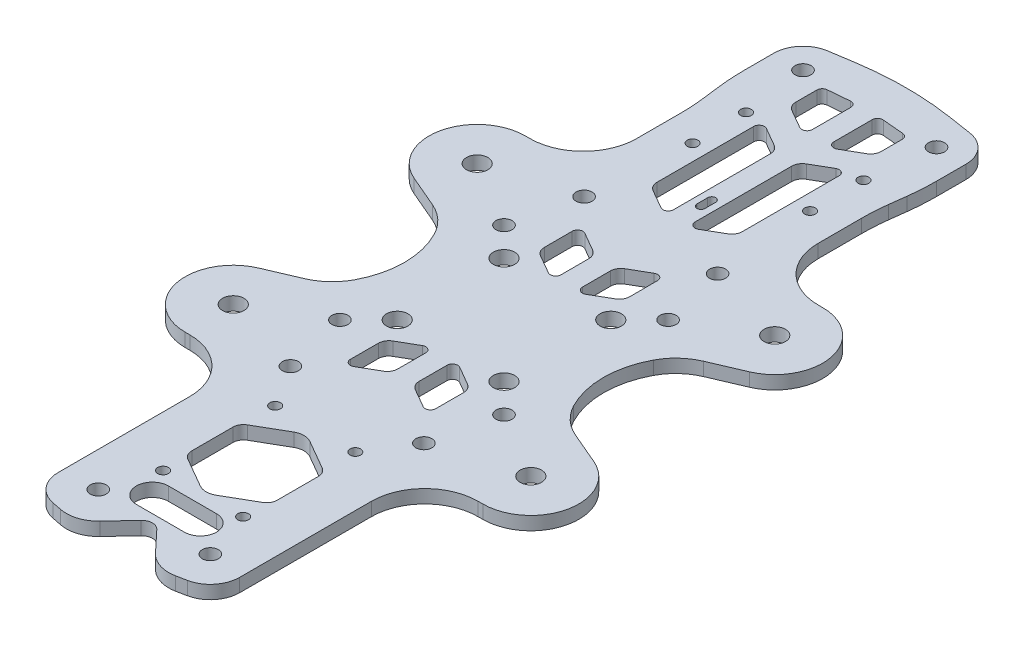
SolidWorks part; units mm, degrees
other "Markup1"
sketch "Sketch3" plane through (-36.8644, 3, -75.3176) normal (0, 1, 0) x (1, 0, 0)
material "Thornel Mat VMA"
ref_plane "Front Plane" through (0, 0, 0) normal (0, 0, 1) x (1, 0, 0)
ref_plane "Top Plane" through (0, 0, 0) normal (0, 1, 0) x (1, 0, 0)
ref_plane "Right Plane" through (0, 0, 0) normal (1, 0, 0) x (0, 0, -1)
sketch "Sketch1" plane through (0, 0, 0) normal (0, 1, 0) x (1, 0, 0)
  line L0 (7.0144, -13.8425) -> (3.5179, -11.8157)
  line L1 (-1.9927, -17.8721) -> (-1.9837, -12.6721)
  line L2 (-6.9856, 13.8181) -> (-3.4821, 11.8035)
  line L3 (2.0122, 17.9008) -> (2.0164, 12.6801)
  line L4 (2, 51.8812) -> (2, 33.7679)
  line L5 (-7, 34.9226) -> (-3.5, 32.9019)
  line L6 (3.5, 58.9019) -> (7, 60.9226)
  line L7 (-7, 60.9226) -> (-3.5, 58.9019)
  line L8 (-1.5, -37.866) -> (-7, -41.0415)
  line L9 (-6.6638, -69.1081) -> (-2.9181, -65.1127)
  line L10 (2.0164, -12.6801) -> (2.0122, -17.9008)
  line L11 (3, -19.6132) -> (6.5, -21.634)
  line L12 (8.002, -20.7686) -> (8.0113, -15.5764)
  line L13 (-3.4821, -11.8035) -> (-6.9856, -13.8181)
  line L14 (-7.9886, -15.5483) -> (-7.9977, -20.7675)
  line L15 (-6.5, -21.634) -> (-3, -19.6133)
  line L16 (-1.9837, 12.6721) -> (-1.9927, 17.8721)
  line L17 (-3, 19.6133) -> (-6.5, 21.634)
  line L18 (-7.9977, 20.7675) -> (-7.9886, 15.5483)
  line L19 (3.5179, 11.8157) -> (7.0144, 13.8425)
  line L20 (8.0113, 15.5764) -> (8.002, 20.7686)
  line L21 (6.5, 21.634) -> (3, 19.6132)
  line L22 (3.5, 32.9019) -> (7, 34.9226)
  line L23 (8, 36.6547) -> (8, 54.7679)
  line L24 (6.5, 55.634) -> (3, 53.6132)
  line L25 (-2, 33.7679) -> (-2, 51.8812)
  line L26 (-3, 53.6133) -> (-6.5, 55.634)
  line L27 (-8, 54.7679) -> (-8, 36.6546)
  line L28 (8, 62.6547) -> (8, 66.5946)
  line L29 (7.0872, 67.5908) -> (3.0872, 67.9408)
  line L30 (2, 66.9446) -> (2, 59.7679)
  line L31 (-2, 59.7679) -> (-2, 66.9446)
  line L32 (-3.0872, 67.9408) -> (-7.0872, 67.5908)
  line L33 (-8, 66.5946) -> (-8, 62.6547)
  line L34 (-8, -42.7735) -> (-8, -50.4641)
  line L35 (-7, -52.1962) -> (-1.5, -55.3716)
  line L36 (1.5, -55.3716) -> (7, -52.1962)
  line L37 (8, -50.4641) -> (8, -42.7735)
  line L38 (7, -41.0415) -> (1.5, -37.866)
  line L39 (-12.1839, -69.9325) -> (-10.3636, -70.2952)
  line L40 (-15, -41.84) -> (-15, -66.5)
  line L41 (-27.8644, -29.84) -> (-27, -29.84)
  line L42 (-24.6147, -13.8367) -> (-30.6171, -16.404)
  line L43 (-30.6171, 16.404) -> (-24.6147, 13.8367)
  line L44 (-26.9944, 29.84) -> (-27.8644, 29.84)
  line L45 (-14.9906, 49.9801) -> (-14.9944, 41.8344)
  line L46 (-15.6838, 58.0267) -> (-15.3029, 54.9969)
  line L47 (-16, 68.4976) -> (-15.9961, 62.9879)
  line L48 (-8.6637, 72.6434) -> (-13.0415, 71.9578)
  line L49 (13.0415, 71.9578) -> (8.6635, 72.6434)
  line L50 (15.9961, 62.9879) -> (15.9999, 68.4976)
  line L51 (15.3029, 54.9969) -> (15.6838, 58.0267)
  line L52 (14.9944, 41.8344) -> (14.9906, 49.98)
  line L53 (27.8644, 29.84) -> (26.9944, 29.84)
  line L54 (24.6147, 13.8367) -> (30.6171, 16.404)
  line L55 (30.6171, -16.404) -> (24.6147, -13.8367)
  line L56 (27, -29.84) -> (27.8644, -29.84)
  line L57 (15, -66.5) -> (15, -41.84)
  line L58 (10.3636, -70.2952) -> (12.1839, -69.9325)
  line L59 (2.9181, -65.1127) -> (6.6638, -69.1081)
  circle A0 centre (15.365, 15.365) radius 1.5
  circle A1 centre (15.365, -15.365) radius 1.5
  circle A2 centre (-15.365, -15.365) radius 1.5
  circle A3 centre (-15.365, 15.365) radius 1.5
  circle A4 centre (27.8644, -22.84) radius 2
  circle A5 centre (27.8644, 22.84) radius 2
  circle A6 centre (10.5, -65.5) radius 1.5
  circle A7 centre (-10, 10) radius 2
  circle A8 centre (-10, -10) radius 2
  circle A9 centre (-10.5, -65.5) radius 1.5
  circle A10 centre (-27.8644, -22.84) radius 2
  circle A11 centre (-27.8644, 22.84) radius 2
  circle A12 centre (12.5, 68.5) radius 1.5
  circle A13 centre (-12.5, 68.5) radius 1.5
  circle A14 centre (-10, -36.5) radius 1
  circle A15 centre (12.5, 27.5) radius 1.5
  circle A16 centre (-10, -56.5) radius 1
  circle A17 centre (-12.5, 27.5) radius 1.5
  circle A18 centre (12.5, -27.5) radius 1.5
  circle A19 centre (10, -36.5) radius 1
  circle A20 centre (-12.5, -27.5) radius 1.5
  circle A21 centre (10, -56.5) radius 1
  circle A22 centre (10, 10) radius 2
  circle A23 centre (10, -10) radius 2
  arc A24 (3.5179, -11.8157) -> (2.0164, -12.6801) centre (3.0164, -12.6808) ccw
  arc A25 (2.0122, -17.9008) -> (3, -19.6132) centre (3.9878, -17.9024) ccw
  arc A26 (6.5, -21.634) -> (8.002, -20.7686) centre (7.0007, -20.7668) ccw
  arc A27 (8.0113, -15.5764) -> (7.0144, -13.8425) centre (6.0113, -15.5728) ccw
  arc A28 (-1.9837, -12.6721) -> (-3.4821, -11.8035) centre (-2.9836, -12.6704) ccw
  arc A29 (-6.9856, -13.8181) -> (-7.9886, -15.5483) centre (-5.9887, -15.5518) ccw
  arc A30 (-7.9977, -20.7675) -> (-6.5, -21.634) centre (-6.9992, -20.7693) ccw
  arc A31 (-3, -19.6133) -> (-1.9927, -17.8721) centre (-4.0073, -17.8686) ccw
  arc A32 (-3.4821, 11.8035) -> (-1.9837, 12.6721) centre (-2.9836, 12.6704) ccw
  arc A33 (-1.9927, 17.8721) -> (-3, 19.6133) centre (-4.0073, 17.8686) ccw
  arc A34 (-6.5, 21.634) -> (-7.9977, 20.7675) centre (-6.9992, 20.7693) ccw
  arc A35 (-7.9886, 15.5483) -> (-6.9856, 13.8181) centre (-5.9887, 15.5518) ccw
  arc A36 (2.0164, 12.6801) -> (3.5179, 11.8157) centre (3.0164, 12.6808) ccw
  arc A37 (7.0144, 13.8425) -> (8.0113, 15.5764) centre (6.0113, 15.5728) ccw
  arc A38 (8.002, 20.7686) -> (6.5, 21.634) centre (7.0007, 20.7668) ccw
  arc A39 (3, 19.6132) -> (2.0122, 17.9008) centre (3.9878, 17.9024) ccw
  arc A40 (2, 33.7679) -> (3.5, 32.9019) centre (3, 33.7679) ccw
  arc A41 (7, 34.9226) -> (8, 36.6547) centre (6, 36.6547) ccw
  arc A42 (8, 54.7679) -> (6.5, 55.634) centre (7, 54.7679) ccw
  arc A43 (3, 53.6132) -> (2, 51.8812) centre (4, 51.8812) ccw
  arc A44 (-3.5, 32.9019) -> (-2, 33.7679) centre (-3, 33.7679) ccw
  arc A45 (-2, 51.8812) -> (-3, 53.6133) centre (-4, 51.8812) ccw
  arc A46 (-6.5, 55.634) -> (-8, 54.7679) centre (-7, 54.7679) ccw
  arc A47 (-8, 36.6546) -> (-7, 34.9226) centre (-6, 36.6546) ccw
  arc A48 (7, 60.9226) -> (8, 62.6547) centre (6, 62.6547) ccw
  arc A49 (8, 66.5946) -> (7.0872, 67.5908) centre (7, 66.5946) ccw
  arc A50 (3.0872, 67.9408) -> (2, 66.9446) centre (3, 66.9446) ccw
  arc A51 (2, 59.7679) -> (3.5, 58.9019) centre (3, 59.7679) ccw
  arc A52 (-3.5, 58.9019) -> (-2, 59.7679) centre (-3, 59.7679) ccw
  arc A53 (-2, 66.9446) -> (-3.0872, 67.9408) centre (-3, 66.9446) ccw
  arc A54 (-7.0872, 67.5908) -> (-8, 66.5946) centre (-7, 66.5946) ccw
  arc A55 (-8, 62.6547) -> (-7, 60.9226) centre (-6, 62.6547) ccw
  arc A56 (-7, -41.0415) -> (-8, -42.7735) centre (-6, -42.7735) ccw
  arc A57 (-8, -50.4641) -> (-7, -52.1962) centre (-6, -50.4641) ccw
  arc A58 (-1.5, -55.3716) -> (1.5, -55.3716) centre (0, -52.7735) ccw
  arc A59 (7, -52.1962) -> (8, -50.4641) centre (6, -50.4641) ccw
  arc A60 (8, -42.7735) -> (7, -41.0415) centre (6, -42.7735) ccw
  arc A61 (1.5, -37.866) -> (-1.5, -37.866) centre (0, -40.4641) ccw
  arc A62 (-10.3636, -70.2952) -> (-6.6638, -69.1081) centre (-9.582, -66.3723) ccw
  arc A63 (-15, -66.5) -> (-12.1839, -69.9325) centre (-11.5, -66.5) ccw
  arc A64 (-15, -41.84) -> (-27, -29.84) centre (-27, -41.84) ccw
  arc A65 (-30.6171, -16.404) -> (-27.8644, -29.84) centre (-27.8644, -22.84) ccw
  arc A66 (-24.6147, -13.8367) -> (-18.7242, -8.4106) centre (-29.3336, -2.8035) ccw
  arc A67 (-18.7242, -8.4106) -> (-18.7242, 8.4106) centre (-34.6384, 0) ccw
  arc A68 (-18.7242, 8.4106) -> (-24.6147, 13.8367) centre (-29.3336, 2.8035) ccw
  arc A69 (-27.8644, 29.84) -> (-30.6171, 16.404) centre (-27.8644, 22.84) ccw
  arc A70 (-26.9944, 29.84) -> (-14.9944, 41.8344) centre (-26.9944, 41.84) ccw
  arc A71 (-14.9906, 49.9801) -> (-15.3029, 54.9969) centre (-54.9906, 50.008) ccw
  arc A72 (-15.9961, 62.9879) -> (-15.6838, 58.0267) centre (24.0039, 63.0156) ccw
  arc A73 (-13.0415, 71.9578) -> (-16, 68.4976) centre (-12.5, 68.5) ccw
  arc A74 (8.6635, 72.6434) -> (-8.6637, 72.6434) centre (-0.0001, 17.3176) ccw
  arc A75 (15.9999, 68.4976) -> (13.0415, 71.9578) centre (12.5, 68.5) ccw
  arc A76 (15.6838, 58.0267) -> (15.9961, 62.9879) centre (-24.0039, 63.0156) ccw
  arc A77 (15.3029, 54.9969) -> (14.9906, 49.98) centre (54.9906, 50.008) ccw
  arc A78 (14.9944, 41.8344) -> (26.9944, 29.84) centre (26.9944, 41.84) ccw
  arc A79 (30.6171, 16.404) -> (27.8644, 29.84) centre (27.8644, 22.84) ccw
  arc A80 (24.6147, 13.8367) -> (18.7242, 8.4106) centre (29.3336, 2.8035) ccw
  arc A81 (18.7242, 8.4106) -> (18.7242, -8.4106) centre (34.6384, 0) ccw
  arc A82 (18.7242, -8.4106) -> (24.6147, -13.8367) centre (29.3336, -2.8035) ccw
  arc A83 (27.8644, -29.84) -> (30.6171, -16.404) centre (27.8644, -22.84) ccw
  arc A84 (27, -29.84) -> (15, -41.84) centre (27, -41.84) ccw
  arc A85 (12.1839, -69.9325) -> (15, -66.5) centre (11.5, -66.5) ccw
  arc A86 (6.6638, -69.1081) -> (10.3636, -70.2952) centre (9.582, -66.3723) ccw
  arc A87 (2.9181, -65.1127) -> (-2.9181, -65.1127) centre (0, -67.8485) ccw
sketch "Sketch2" plane through (0, 0, 0) normal (0, 1, 0) x (1, 0, 0)
  line L0 (-3.5, 32.9019) -> (3.5, 32.9019) construction
  line L5 (0, 38.9019) -> (0, 36.9019) construction
  line L7 (0.75, 38.9019) -> (0.75, 36.9019)
  line L8 (-0.75, 38.9019) -> (-0.75, 36.9019)
  line L9 (0, 0) -> (-0.0001, 75.3176) construction
  line L10 (0, 0) -> (0, -65.8485) construction
  line L11 (-18.6384, 0) -> (18.6384, 0) construction
  line L12 (-4.5, -61.3485) -> (4.5, -61.3485) construction
  line L13 (-4.5, -58.3485) -> (4.5, -58.3485)
  line L14 (-4.5, -64.3485) -> (4.5, -64.3485)
  line L15 (-14.0001, 51.3176) -> (13.9999, 51.3176) construction
  line L16 (-14.0001, 64.3176) -> (13.9999, 64.3176) construction
  line L17 (-14.0001, 64.3176) -> (-14.0001, 44.3176) construction
  line L18 (-14.0001, 44.3176) -> (13.9999, 44.3176) construction
  line L19 (13.9999, 64.3176) -> (13.9999, 44.3176) construction
  line L20 (-14.0001, 64.3176) -> (13.9999, 44.3176) construction
  line L21 (-14.0001, 44.3176) -> (13.9999, 64.3176) construction
  line L22 (-11.0001, 46.3176) -> (10.9999, 46.3176) construction
  line L513 (7, -41.0415) -> (1.5, -37.866) construction
  line L514 (-1.5, -37.866) -> (-7, -41.0415) construction
  line L515 (1.5, -55.3716) -> (7, -52.1962) construction
  line L516 (8, -50.4641) -> (8, -42.7735) construction
  line L517 (-8, -42.7735) -> (-8, -50.4641) construction
  line L518 (-7, -52.1962) -> (-1.5, -55.3716) construction
  line L519 (3, -19.6132) -> (6.5, -21.634) construction
  line L520 (7.0144, -13.8425) -> (3.5179, -11.8157) construction
  line L521 (8.002, -20.7686) -> (8.0113, -15.5764) construction
  line L522 (2.0164, -12.6801) -> (2.0122, -17.9008) construction
  line L523 (-6.5, -21.634) -> (-3, -19.6133) construction
  line L524 (-7.9886, -15.5483) -> (-7.9977, -20.7675) construction
  line L525 (-3.4821, -11.8035) -> (-6.9856, -13.8181) construction
  line L526 (-1.9927, -17.8721) -> (-1.9837, -12.6721) construction
  line L527 (3.5179, 11.8157) -> (7.0144, 13.8425) construction
  line L528 (8.0113, 15.5764) -> (8.002, 20.7686) construction
  line L529 (6.5, 21.634) -> (3, 19.6132) construction
  line L530 (-3, 19.6133) -> (-6.5, 21.634) construction
  line L531 (-7.9977, 20.7675) -> (-7.9886, 15.5483) construction
  line L532 (-1.9837, 12.6721) -> (-1.9927, 17.8721) construction
  line L533 (2.0122, 17.9008) -> (2.0164, 12.6801) construction
  line L534 (-6.9856, 13.8181) -> (-3.4821, 11.8035) construction
  line L535 (13.3509, 73.9337) -> (8.9729, 74.6193)
  line L536 (-8.9731, 74.6193) -> (-13.3509, 73.9338)
  line L537 (-18, 68.4962) -> (-17.9961, 62.9865)
  line L538 (-17.6682, 57.7773) -> (-17.2873, 54.7475)
  line L539 (17.9961, 62.9865) -> (17.9999, 68.4962)
  line L540 (17.2873, 54.7474) -> (17.6682, 57.7773)
  line L541 (-16.9906, 49.981) -> (-16.9944, 41.8353)
  line L542 (16.9944, 41.8353) -> (16.9906, 49.9814)
  line L543 (27.8644, 31.84) -> (26.9944, 31.84)
  line L544 (25.4012, 11.9979) -> (31.4036, 14.5651)
  line L545 (31.4036, -14.5651) -> (25.4012, -11.9979)
  line L546 (27, -31.84) -> (27.8644, -31.84)
  line L547 (17, -66.5) -> (17, -41.84)
  line L548 (10.7545, -72.2567) -> (12.5748, -71.894)
  line L549 (1.4591, -66.4806) -> (5.2048, -70.476)
  line L550 (-5.2048, -70.476) -> (-1.4591, -66.4806)
  line L551 (-12.5748, -71.894) -> (-10.7545, -72.2567)
  line L552 (-17, -41.84) -> (-17, -66.5)
  line L553 (-27.8644, -31.84) -> (-27, -31.84)
  line L554 (-25.4012, -11.9979) -> (-31.4036, -14.5651)
  line L555 (-31.4036, 14.5651) -> (-25.4012, 11.9979)
  line L556 (-26.9944, 31.84) -> (-27.8644, 31.84)
  line L557 (13.3509, 73.9337) -> (8.9729, 74.6193)
  line L558 (-8.9731, 74.6193) -> (-13.3509, 73.9338)
  line L559 (-18, 68.4962) -> (-17.9961, 62.9865)
  line L560 (-17.6682, 57.7773) -> (-17.2873, 54.7475)
  line L561 (17.9961, 62.9865) -> (17.9999, 68.4962)
  line L562 (17.2873, 54.7474) -> (17.6682, 57.7773)
  line L563 (-16.9906, 49.981) -> (-16.9944, 41.8353)
  line L564 (16.9944, 41.8353) -> (16.9906, 49.9814)
  line L565 (27.8644, 31.84) -> (26.9944, 31.84)
  line L566 (25.4012, 11.9979) -> (31.4036, 14.5651)
  line L567 (31.4036, -14.5651) -> (25.4012, -11.9979)
  line L568 (27, -31.84) -> (27.8644, -31.84)
  line L569 (17, -66.5) -> (17, -41.84)
  line L570 (10.7545, -72.2567) -> (12.5748, -71.894)
  line L571 (1.4591, -66.4806) -> (5.2048, -70.476)
  line L572 (-5.2048, -70.476) -> (-1.4591, -66.4806)
  line L573 (-12.5748, -71.894) -> (-10.7545, -72.2567)
  line L574 (-17, -41.84) -> (-17, -66.5)
  line L575 (-27.8644, -31.84) -> (-27, -31.84)
  line L576 (-25.4012, -11.9979) -> (-31.4036, -14.5651)
  line L577 (-31.4036, 14.5651) -> (-25.4012, 11.9979)
  line L578 (-26.9944, 31.84) -> (-27.8644, 31.84)
  line L579 (3.5, 32.9019) -> (7, 34.9226) construction
  line L580 (-7, 34.9226) -> (-3.5, 32.9019) construction
  line L581 (8, 36.6547) -> (8, 54.7679) construction
  line L582 (6.5, 55.634) -> (3, 53.6132) construction
  line L583 (-3, 53.6133) -> (-6.5, 55.634) construction
  line L584 (-2, 33.7679) -> (-2, 51.8812) construction
  line L585 (2, 51.8812) -> (2, 33.7679) construction
  line L586 (-8, 54.7679) -> (-8, 36.6546) construction
  line L587 (3.5, 58.9019) -> (7, 60.9226) construction
  line L588 (8, 62.6547) -> (8, 66.5946) construction
  line L589 (7.0872, 67.5908) -> (3.0872, 67.9408) construction
  line L590 (2, 66.9446) -> (2, 59.7679) construction
  line L591 (-7, 60.9226) -> (-3.5, 58.9019) construction
  line L592 (-2, 59.7679) -> (-2, 66.9446) construction
  line L593 (-3.0872, 67.9408) -> (-7.0872, 67.5908) construction
  line L594 (-8, 66.5946) -> (-8, 62.6547) construction
  line L595 (7, -41.0415) -> (1.5, -37.866)
  line L596 (-1.5, -37.866) -> (-7, -41.0415)
  line L597 (1.5, -55.3716) -> (7, -52.1962)
  line L598 (8, -50.4641) -> (8, -42.7735)
  line L599 (-8, -42.7735) -> (-8, -50.4641)
  line L600 (-7, -52.1962) -> (-1.5, -55.3716)
  line L601 (3, -19.6132) -> (6.5, -21.634)
  line L602 (7.0144, -13.8425) -> (3.5179, -11.8157)
  line L603 (8.002, -20.7686) -> (8.0113, -15.5764)
  line L604 (2.0164, -12.6801) -> (2.0122, -17.9008)
  line L605 (-6.5, -21.634) -> (-3, -19.6133)
  line L606 (-7.9886, -15.5483) -> (-7.9977, -20.7675)
  line L607 (-3.4821, -11.8035) -> (-6.9856, -13.8181)
  line L608 (-1.9927, -17.8721) -> (-1.9837, -12.6721)
  line L609 (3.5179, 11.8157) -> (7.0144, 13.8425)
  line L610 (8.0113, 15.5764) -> (8.002, 20.7686)
  line L611 (6.5, 21.634) -> (3, 19.6132)
  line L612 (-3, 19.6133) -> (-6.5, 21.634)
  line L613 (-7.9977, 20.7675) -> (-7.9886, 15.5483)
  line L614 (-1.9837, 12.6721) -> (-1.9927, 17.8721)
  line L615 (2.0122, 17.9008) -> (2.0164, 12.6801)
  line L616 (-6.9856, 13.8181) -> (-3.4821, 11.8035)
  line L617 (3.5, 32.9019) -> (7, 34.9226)
  line L618 (-7, 34.9226) -> (-3.5, 32.9019)
  line L619 (8, 36.6547) -> (8, 54.7679)
  line L620 (6.5, 55.634) -> (3, 53.6132)
  line L621 (-3, 53.6133) -> (-6.5, 55.634)
  line L622 (-2, 33.7679) -> (-2, 51.8812)
  line L623 (2, 51.8812) -> (2, 33.7679)
  line L624 (-8, 54.7679) -> (-8, 36.6546)
  line L625 (3.5, 58.9019) -> (7, 60.9226)
  line L626 (8, 62.6547) -> (8, 66.5946)
  line L627 (7.0872, 67.5908) -> (3.0872, 67.9408)
  line L628 (2, 66.9446) -> (2, 59.7679)
  line L629 (-7, 60.9226) -> (-3.5, 58.9019)
  line L630 (-2, 59.7679) -> (-2, 66.9446)
  line L631 (-3.0872, 67.9408) -> (-7.0872, 67.5908)
  line L632 (-8, 66.5946) -> (-8, 62.6547)
  arc A1 (0.75, 38.9019) -> (-0.75, 38.9019) centre (0, 38.9019) ccw
  arc A2 (-0.75, 36.9019) -> (0.75, 36.9019) centre (0, 36.9019) ccw
  circle A3 centre (-12.5, 68.5) radius 2.75 construction
  circle A4 centre (12.4998, 68.5) radius 2.75 construction
  circle A5 centre (-7.5, -35.3485) radius 1
  circle A6 centre (-7.5, -56.3485) radius 1
  circle A7 centre (7.5, -35.3485) radius 1
  circle A8 centre (7.5, -56.3485) radius 1
  arc A9 (-4.5, -58.3485) -> (-4.5, -64.3485) centre (-4.5, -61.3485) ccw
  arc A10 (4.5, -64.3485) -> (4.5, -58.3485) centre (4.5, -61.3485) ccw
  circle A11 centre (-10.5, -65.5) radius 2.75 construction
  circle A12 centre (10.5, -65.5) radius 2.75 construction
  circle A16 centre (-11.0001, 46.3176) radius 1
  circle A17 centre (10.9999, 46.3176) radius 1
  circle A18 centre (10.9999, 56.3176) radius 1
  circle A19 centre (-11.0001, 56.3176) radius 1
  arc A666 (8, -42.7735) -> (7, -41.0415) centre (6, -42.7735) ccw construction
  arc A667 (1.5, -37.866) -> (-1.5, -37.866) centre (0, -40.4641) ccw construction
  arc A668 (-7, -41.0415) -> (-8, -42.7735) centre (-6, -42.7735) ccw construction
  arc A669 (-8, -50.4641) -> (-7, -52.1962) centre (-6, -50.4641) ccw construction
  arc A670 (-1.5, -55.3716) -> (1.5, -55.3716) centre (0, -52.7735) ccw construction
  arc A671 (7, -52.1962) -> (8, -50.4641) centre (6, -50.4641) ccw construction
  circle A674 centre (10.5, -65.5) radius 1.5 construction
  circle A675 centre (-10.5, -65.5) radius 1.5 construction
  arc A676 (6.5, -21.634) -> (8.002, -20.7686) centre (7.0007, -20.7668) ccw construction
  arc A677 (2.0122, -17.9008) -> (3, -19.6132) centre (3.9878, -17.9024) ccw construction
  arc A678 (3.5179, -11.8157) -> (2.0164, -12.6801) centre (3.0164, -12.6808) ccw construction
  arc A679 (8.0113, -15.5764) -> (7.0144, -13.8425) centre (6.0113, -15.5728) ccw construction
  arc A680 (-3, -19.6133) -> (-1.9927, -17.8721) centre (-4.0073, -17.8686) ccw construction
  arc A681 (-7.9977, -20.7675) -> (-6.5, -21.634) centre (-6.9992, -20.7693) ccw construction
  arc A682 (-6.9856, -13.8181) -> (-7.9886, -15.5483) centre (-5.9887, -15.5518) ccw construction
  arc A683 (-1.9837, -12.6721) -> (-3.4821, -11.8035) centre (-2.9836, -12.6704) ccw construction
  circle A684 centre (10, -10) radius 2 construction
  circle A685 centre (15.365, -15.365) radius 1.5 construction
  circle A686 centre (27.8644, -22.84) radius 2 construction
  circle A687 centre (12.5, -27.5) radius 1.5 construction
  circle A690 centre (-10, -10) radius 2 construction
  circle A691 centre (-15.365, -15.365) radius 1.5 construction
  arc A692 (8.9729, 74.6193) -> (-8.9731, 74.6193) centre (-0.0001, 17.3176) ccw
  arc A693 (-13.3509, 73.9338) -> (-18, 68.4962) centre (-12.5, 68.5) ccw
  arc A694 (-17.9961, 62.9865) -> (-17.6682, 57.7773) centre (24.0039, 63.0156) ccw
  arc A695 (17.9999, 68.4962) -> (13.3509, 73.9337) centre (12.5, 68.5) ccw
  arc A696 (17.6682, 57.7773) -> (17.9961, 62.9865) centre (-24.0039, 63.0156) ccw
  arc A697 (-16.9906, 49.981) -> (-17.2873, 54.7475) centre (-54.9906, 50.008) ccw
  arc A698 (17.2873, 54.7474) -> (16.9906, 49.9814) centre (54.9906, 50.008) ccw
  arc A699 (16.9944, 41.8353) -> (26.9944, 31.84) centre (26.9944, 41.84) ccw
  arc A700 (31.4036, 14.5651) -> (27.8644, 31.84) centre (27.8644, 22.84) ccw
  arc A701 (25.4012, 11.9979) -> (20.4924, 7.4761) centre (29.3336, 2.8035) ccw
  arc A702 (20.4924, 7.4761) -> (20.4924, -7.4761) centre (34.6384, 0) ccw
  arc A703 (20.4924, -7.4761) -> (25.4012, -11.9979) centre (29.3336, -2.8035) ccw
  arc A704 (27.8644, -31.84) -> (31.4036, -14.5651) centre (27.8644, -22.84) ccw
  arc A705 (27, -31.84) -> (17, -41.84) centre (27, -41.84) ccw
  arc A706 (12.5748, -71.894) -> (17, -66.5) centre (11.5, -66.5) ccw
  arc A707 (5.2048, -70.476) -> (10.7545, -72.2567) centre (9.582, -66.3723) ccw
  arc A708 (1.4591, -66.4806) -> (-1.4591, -66.4806) centre (0, -67.8485) ccw
  arc A709 (-10.7545, -72.2567) -> (-5.2048, -70.476) centre (-9.582, -66.3723) ccw
  arc A710 (-17, -66.5) -> (-12.5748, -71.894) centre (-11.5, -66.5) ccw
  arc A711 (-17, -41.84) -> (-27, -31.84) centre (-27, -41.84) ccw
  arc A712 (-31.4036, -14.5651) -> (-27.8644, -31.84) centre (-27.8644, -22.84) ccw
  arc A713 (-25.4012, -11.9979) -> (-20.4924, -7.4761) centre (-29.3336, -2.8035) ccw
  arc A714 (-20.4924, -7.4761) -> (-20.4924, 7.4761) centre (-34.6384, 0) ccw
  arc A715 (-20.4924, 7.4761) -> (-25.4012, 11.9979) centre (-29.3336, 2.8035) ccw
  arc A716 (-27.8644, 31.84) -> (-31.4036, 14.5651) centre (-27.8644, 22.84) ccw
  arc A717 (-26.9944, 31.84) -> (-16.9944, 41.8353) centre (-26.9944, 41.84) ccw
  arc A718 (8.9729, 74.6193) -> (-8.9731, 74.6193) centre (-0.0001, 17.3176) ccw
  arc A719 (-13.3509, 73.9338) -> (-18, 68.4962) centre (-12.5, 68.5) ccw
  arc A720 (-17.9961, 62.9865) -> (-17.6682, 57.7773) centre (24.0039, 63.0156) ccw
  arc A721 (17.9999, 68.4962) -> (13.3509, 73.9337) centre (12.5, 68.5) ccw
  arc A722 (17.6682, 57.7773) -> (17.9961, 62.9865) centre (-24.0039, 63.0156) ccw
  arc A723 (-16.9906, 49.981) -> (-17.2873, 54.7475) centre (-54.9906, 50.008) ccw
  arc A724 (17.2873, 54.7474) -> (16.9906, 49.9814) centre (54.9906, 50.008) ccw
  arc A725 (16.9944, 41.8353) -> (26.9944, 31.84) centre (26.9944, 41.84) ccw
  arc A726 (31.4036, 14.5651) -> (27.8644, 31.84) centre (27.8644, 22.84) ccw
  arc A727 (25.4012, 11.9979) -> (20.4924, 7.4761) centre (29.3336, 2.8035) ccw
  arc A728 (20.4924, 7.4761) -> (20.4924, -7.4761) centre (34.6384, 0) ccw
  arc A729 (20.4924, -7.4761) -> (25.4012, -11.9979) centre (29.3336, -2.8035) ccw
  arc A730 (27.8644, -31.84) -> (31.4036, -14.5651) centre (27.8644, -22.84) ccw
  arc A731 (27, -31.84) -> (17, -41.84) centre (27, -41.84) ccw
  arc A732 (12.5748, -71.894) -> (17, -66.5) centre (11.5, -66.5) ccw
  arc A733 (5.2048, -70.476) -> (10.7545, -72.2567) centre (9.582, -66.3723) ccw
  arc A734 (1.4591, -66.4806) -> (-1.4591, -66.4806) centre (0, -67.8485) ccw
  arc A735 (-10.7545, -72.2567) -> (-5.2048, -70.476) centre (-9.582, -66.3723) ccw
  arc A736 (-17, -66.5) -> (-12.5748, -71.894) centre (-11.5, -66.5) ccw
  arc A737 (-17, -41.84) -> (-27, -31.84) centre (-27, -41.84) ccw
  arc A738 (-31.4036, -14.5651) -> (-27.8644, -31.84) centre (-27.8644, -22.84) ccw
  arc A739 (-25.4012, -11.9979) -> (-20.4924, -7.4761) centre (-29.3336, -2.8035) ccw
  arc A740 (-20.4924, -7.4761) -> (-20.4924, 7.4761) centre (-34.6384, 0) ccw
  arc A741 (-20.4924, 7.4761) -> (-25.4012, 11.9979) centre (-29.3336, 2.8035) ccw
  arc A742 (-27.8644, 31.84) -> (-31.4036, 14.5651) centre (-27.8644, 22.84) ccw
  arc A743 (-26.9944, 31.84) -> (-16.9944, 41.8353) centre (-26.9944, 41.84) ccw
  circle A744 centre (-12.5, -27.5) radius 1.5 construction
  circle A745 centre (-27.8644, -22.84) radius 2 construction
  circle A746 centre (27.8644, 22.84) radius 2 construction
  circle A747 centre (15.365, 15.365) radius 1.5 construction
  circle A748 centre (10, 10) radius 2 construction
  arc A749 (2.0164, 12.6801) -> (3.5179, 11.8157) centre (3.0164, 12.6808) ccw construction
  arc A750 (7.0144, 13.8425) -> (8.0113, 15.5764) centre (6.0113, 15.5728) ccw construction
  arc A751 (8.002, 20.7686) -> (6.5, 21.634) centre (7.0007, 20.7668) ccw construction
  arc A752 (3, 19.6132) -> (2.0122, 17.9008) centre (3.9878, 17.9024) ccw construction
  arc A753 (-1.9927, 17.8721) -> (-3, 19.6133) centre (-4.0073, 17.8686) ccw construction
  arc A754 (-6.5, 21.634) -> (-7.9977, 20.7675) centre (-6.9992, 20.7693) ccw construction
  arc A755 (-7.9886, 15.5483) -> (-6.9856, 13.8181) centre (-5.9887, 15.5518) ccw construction
  arc A756 (-3.4821, 11.8035) -> (-1.9837, 12.6721) centre (-2.9836, 12.6704) ccw construction
  circle A757 centre (-10, 10) radius 2 construction
  circle A758 centre (-15.365, 15.365) radius 1.5 construction
  circle A759 centre (-27.8644, 22.84) radius 2 construction
  circle A760 centre (-12.5, 27.5) radius 1.5 construction
  circle A761 centre (12.5, 27.5) radius 1.5 construction
  arc A762 (7, 34.9226) -> (8, 36.6547) centre (6, 36.6547) ccw construction
  arc A763 (2, 33.7679) -> (3.5, 32.9019) centre (3, 33.7679) ccw construction
  arc A764 (-8, 36.6546) -> (-7, 34.9226) centre (-6, 36.6546) ccw construction
  arc A765 (-3.5, 32.9019) -> (-2, 33.7679) centre (-3, 33.7679) ccw construction
  arc A766 (8, 54.7679) -> (6.5, 55.634) centre (7, 54.7679) ccw construction
  arc A767 (3, 53.6132) -> (2, 51.8812) centre (4, 51.8812) ccw construction
  arc A768 (-2, 51.8812) -> (-3, 53.6133) centre (-4, 51.8812) ccw construction
  arc A769 (-6.5, 55.634) -> (-8, 54.7679) centre (-7, 54.7679) ccw construction
  arc A770 (2, 59.7679) -> (3.5, 58.9019) centre (3, 59.7679) ccw construction
  arc A771 (7, 60.9226) -> (8, 62.6547) centre (6, 62.6547) ccw construction
  arc A772 (8, 66.5946) -> (7.0872, 67.5908) centre (7, 66.5946) ccw construction
  arc A773 (3.0872, 67.9408) -> (2, 66.9446) centre (3, 66.9446) ccw construction
  arc A774 (-8, 62.6547) -> (-7, 60.9226) centre (-6, 62.6547) ccw construction
  arc A775 (-3.5, 58.9019) -> (-2, 59.7679) centre (-3, 59.7679) ccw construction
  arc A776 (-2, 66.9446) -> (-3.0872, 67.9408) centre (-3, 66.9446) ccw construction
  arc A777 (-7.0872, 67.5908) -> (-8, 66.5946) centre (-7, 66.5946) ccw construction
  circle A778 centre (-12.5, 68.5) radius 1.5 construction
  circle A779 centre (12.5, 68.5) radius 1.5 construction
  arc A780 (8, -42.7735) -> (7, -41.0415) centre (6, -42.7735) ccw
  arc A781 (1.5, -37.866) -> (-1.5, -37.866) centre (0, -40.4641) ccw
  arc A782 (-7, -41.0415) -> (-8, -42.7735) centre (-6, -42.7735) ccw
  arc A783 (-8, -50.4641) -> (-7, -52.1962) centre (-6, -50.4641) ccw
  arc A784 (-1.5, -55.3716) -> (1.5, -55.3716) centre (0, -52.7735) ccw
  arc A785 (7, -52.1962) -> (8, -50.4641) centre (6, -50.4641) ccw
  circle A788 centre (10.5, -65.5) radius 1.5
  circle A789 centre (-10.5, -65.5) radius 1.5
  arc A790 (6.5, -21.634) -> (8.002, -20.7686) centre (7.0007, -20.7668) ccw
  arc A791 (2.0122, -17.9008) -> (3, -19.6132) centre (3.9878, -17.9024) ccw
  arc A792 (3.5179, -11.8157) -> (2.0164, -12.6801) centre (3.0164, -12.6808) ccw
  arc A793 (8.0113, -15.5764) -> (7.0144, -13.8425) centre (6.0113, -15.5728) ccw
  arc A794 (-3, -19.6133) -> (-1.9927, -17.8721) centre (-4.0073, -17.8686) ccw
  arc A795 (-7.9977, -20.7675) -> (-6.5, -21.634) centre (-6.9992, -20.7693) ccw
  arc A796 (-6.9856, -13.8181) -> (-7.9886, -15.5483) centre (-5.9887, -15.5518) ccw
  arc A797 (-1.9837, -12.6721) -> (-3.4821, -11.8035) centre (-2.9836, -12.6704) ccw
  circle A798 centre (10, -10) radius 2
  circle A799 centre (15.365, -15.365) radius 1.5
  circle A800 centre (27.8644, -22.84) radius 2
  circle A801 centre (12.5, -27.5) radius 1.5
  circle A804 centre (-10, -10) radius 2
  circle A805 centre (-15.365, -15.365) radius 1.5
  circle A806 centre (-12.5, -27.5) radius 1.5
  circle A807 centre (-27.8644, -22.84) radius 2
  circle A808 centre (27.8644, 22.84) radius 2
  circle A809 centre (15.365, 15.365) radius 1.5
  circle A810 centre (10, 10) radius 2
  arc A811 (2.0164, 12.6801) -> (3.5179, 11.8157) centre (3.0164, 12.6808) ccw
  arc A812 (7.0144, 13.8425) -> (8.0113, 15.5764) centre (6.0113, 15.5728) ccw
  arc A813 (8.002, 20.7686) -> (6.5, 21.634) centre (7.0007, 20.7668) ccw
  arc A814 (3, 19.6132) -> (2.0122, 17.9008) centre (3.9878, 17.9024) ccw
  arc A815 (-1.9927, 17.8721) -> (-3, 19.6133) centre (-4.0073, 17.8686) ccw
  arc A816 (-6.5, 21.634) -> (-7.9977, 20.7675) centre (-6.9992, 20.7693) ccw
  arc A817 (-7.9886, 15.5483) -> (-6.9856, 13.8181) centre (-5.9887, 15.5518) ccw
  arc A818 (-3.4821, 11.8035) -> (-1.9837, 12.6721) centre (-2.9836, 12.6704) ccw
  circle A819 centre (-10, 10) radius 2
  circle A820 centre (-15.365, 15.365) radius 1.5
  circle A821 centre (-27.8644, 22.84) radius 2
  circle A822 centre (-12.5, 27.5) radius 1.5
  circle A823 centre (12.5, 27.5) radius 1.5
  arc A824 (7, 34.9226) -> (8, 36.6547) centre (6, 36.6547) ccw
  arc A825 (2, 33.7679) -> (3.5, 32.9019) centre (3, 33.7679) ccw
  arc A826 (-8, 36.6546) -> (-7, 34.9226) centre (-6, 36.6546) ccw
  arc A827 (-3.5, 32.9019) -> (-2, 33.7679) centre (-3, 33.7679) ccw
  arc A828 (8, 54.7679) -> (6.5, 55.634) centre (7, 54.7679) ccw
  arc A829 (3, 53.6132) -> (2, 51.8812) centre (4, 51.8812) ccw
  arc A830 (-2, 51.8812) -> (-3, 53.6133) centre (-4, 51.8812) ccw
  arc A831 (-6.5, 55.634) -> (-8, 54.7679) centre (-7, 54.7679) ccw
  arc A832 (2, 59.7679) -> (3.5, 58.9019) centre (3, 59.7679) ccw
  arc A833 (7, 60.9226) -> (8, 62.6547) centre (6, 62.6547) ccw
  arc A834 (8, 66.5946) -> (7.0872, 67.5908) centre (7, 66.5946) ccw
  arc A835 (3.0872, 67.9408) -> (2, 66.9446) centre (3, 66.9446) ccw
  arc A836 (-8, 62.6547) -> (-7, 60.9226) centre (-6, 62.6547) ccw
  arc A837 (-3.5, 58.9019) -> (-2, 59.7679) centre (-3, 59.7679) ccw
  arc A838 (-2, 66.9446) -> (-3.0872, 67.9408) centre (-3, 66.9446) ccw
  arc A839 (-7.0872, 67.5908) -> (-8, 66.5946) centre (-7, 66.5946) ccw
  circle A840 centre (-12.5, 68.5) radius 1.5
  circle A841 centre (12.5, 68.5) radius 1.5
  point P26 (0, 37.9019)
  point P33 (0.75, 37.9019)
  point P72 (0, 0)
  point P75 (0, 32.9019)
  point P138 (0, -61.3485)
  point P165 (-0.0001, 54.3176)
  point P190 (-0.0001, 46.3176)
  dimension "D2" = 1.5
  dimension "D10" = 20
  dimension "D15" = 11
  dimension "D14" = 28
  dimension "D16" = 2
  dimension "D17" = 2
  dimension "D18" = 2
  dimension "D3" = 2
  dimension "D4" = 5
  dimension "12.5" = 9
  dimension "D11" = 6
  dimension "D12" = 1.5
  dimension "D19" = 22
  dimension "D20" = 7
  dimension "D1" = 2
extrude "Boss-Extrude1" add sketch "Sketch2" along normal blind 2.5
